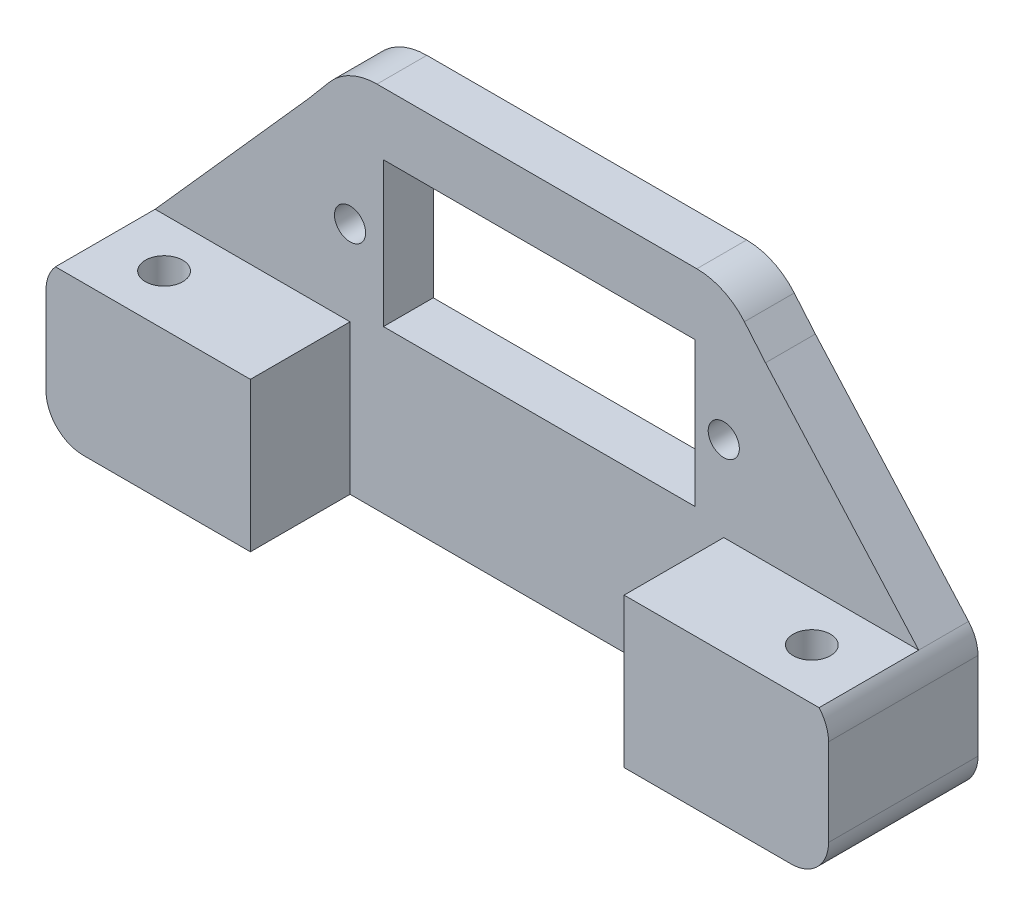
SolidWorks part; units mm, degrees
ref_plane "前视基准面" through (0, 0, 0) normal (0, 0, 1) x (1, 0, 0)
ref_plane "上视基准面" through (0, 0, 0) normal (0, 1, 0) x (1, 0, 0)
ref_plane "右视基准面" through (0, 0, 0) normal (1, 0, 0) x (0, 0, -1)
sketch "草图1" plane through (0, 0, 0) normal (0, 0, 1) x (1, 0, 0)
  line L1 (18.5714, 0) -> (41.2714, 0)
  line L3 (0.1827, -29.6) -> (57, -29.6)
  line L4 (60, -19.6) -> (60, -26.6)
  line L5 (18.5714, 0) -> (41.2714, 0)
  line L6 (53, -17.607) -> (59.2419, -17.607)
  line L7 (59.2419, -17.607) -> (46.9439, -3.7813)
  line L8 (46.9439, -3.7813) -> (45.2486, -1.7739)
  line L9 (41.4286, 0) -> (41.2714, 0)
  line L10 (28.5914, 7.9252) -> (28.5914, -33.8061) construction
  line L12 (-2.8173, -19.6) -> (-2.8173, -26.6)
  line L13 (4.1827, -17.607) -> (-2.0591, -17.607)
  line L14 (10.2388, -3.7813) -> (11.9342, -1.7739)
  line L15 (-2.0591, -17.607) -> (10.2388, -3.7813)
  line L16 (18.5714, 0) -> (15.7541, 0)
  line L17 (16.2714, -5) -> (41.2714, -5)
  line L18 (16.2714, -5) -> (16.2714, -16.6)
  line L19 (16.2714, -16.6) -> (41.2714, -16.6)
  line L20 (41.2714, -5) -> (41.2714, -16.6)
  line L21 (10.2388, -3.7813) -> (-2.0591, -17.607)
  line L22 (4.1827, -17.607) -> (13.5914, -17.607)
  line L23 (13.5914, -17.607) -> (13.5914, -29.6)
  line L24 (13.5914, -29.6) -> (4.1827, -29.6)
  line L25 (43.5914, -17.607) -> (43.5914, -29.6)
  line L26 (53, -17.607) -> (43.5914, -17.607)
  line L27 (43.5914, -29.6) -> (53, -29.6)
  arc A0 (60, -19.6) -> (59.2419, -17.607) centre (57.0013, -19.6) ccw
  arc A1 (45.2486, -1.7739) -> (41.4286, 0) centre (41.4286, -5) ccw
  arc A2 (57, -29.6) -> (60, -26.6) centre (57, -26.6) ccw
  arc A3 (0.1827, -29.6) -> (-2.8173, -26.6) centre (0.1827, -26.6) cw
  arc A4 (-2.8173, -19.6) -> (-2.0591, -17.607) centre (0.1815, -19.6) cw
  arc A5 (11.9342, -1.7739) -> (15.7541, 0) centre (15.7541, -5) cw
  circle A6 centre (43.5914, -10.8) radius 1.25
  circle A9 centre (13.5914, -10.8) radius 1.25
  point P36 (41.2714, -10.8)
  dimension "D2" = 10
  dimension "D7" = 5
  dimension "D8" = 3
  dimension "D10" = 2.5
  dimension "D1" = 25
  dimension "D3" = 22.7
  dimension "D4" = 48.347
  dimension "D5" = 11.6
  dimension "D6" = 11.993
  dimension "D9" = 5
  dimension "D11" = 2.32
  dimension "D14" = 30
extrude "凸台-拉伸2" add sketch "草图1" along normal blind 4 contours L10 L1 A5 L14 L15 L13 L3 L19 L18 L17 A9 | L5 L10 L17 L20 L19 L3 L6 L7 L8 A1 L9 A6 region at (23.5814, -0.4261, 0) region at (34.9314, -0.4261, 0)
extrude "凸台-拉伸3" add sketch "草图1<4>" along normal blind 12 contours A4 L12 A3 L3 L13 | L3 A2 L4 A0 L6 region at (5.4814, -23.564, 0) region at (51.7013, -23.564, 0)
sketch "草图1<4>" plane through (0, 0, 0) normal (0, 0, 1) x (1, 0, 0) same geometry as "草图1"
sketch "草图2" plane through (0, -17.607, 0) normal (0, 1, 0) x (1, 0, 0)
  line L0 (28.5914, -13.1416) -> (28.5914, 7.9786) construction
  circle A0 centre (2.5914, -7.9293) radius 1.5
  circle A1 centre (54.5914, -7.9293) radius 1.5
  dimension "D1" = 3
  dimension "D2" = 26
extrude "切除-拉伸1" cut sketch "草图2" against normal through all
